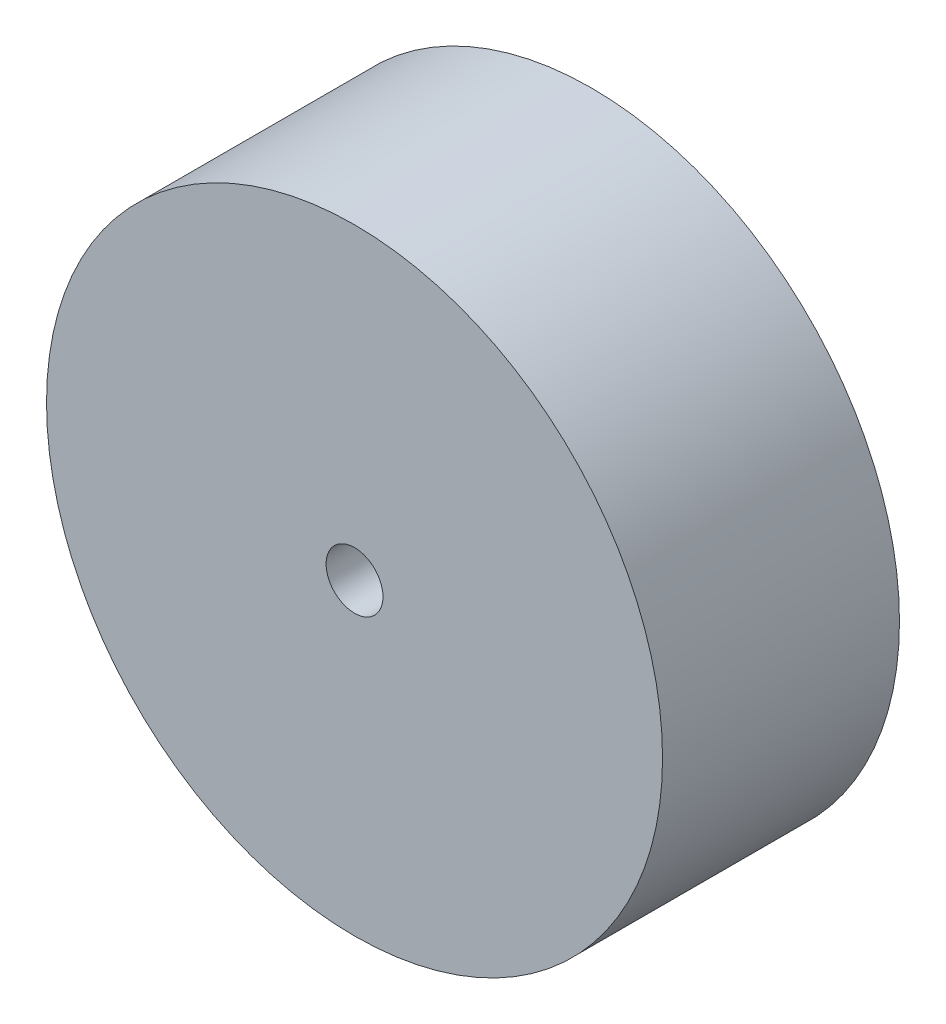
SolidWorks part; units mm, degrees
ref_plane "Plan de face" through (0, 0, 0) normal (0, 0, 1) x (1, 0, 0)
ref_plane "Plan de dessus" through (0, 0, 0) normal (0, 1, 0) x (1, 0, 0)
ref_plane "Plan de droite" through (0, 0, 0) normal (1, 0, 0) x (0, 0, -1)
sketch "Esquisse1" plane through (0, 0, 0) normal (0, 0, 1) x (1, 0, 0)
  circle A0 centre (0, 0) radius 32.5
  circle A1 centre (0, 0) radius 3
  dimension "D1" = 65
  dimension "D2" = 6
extrude "Boss.-Extru.1" add sketch "Esquisse1" along normal blind 25
